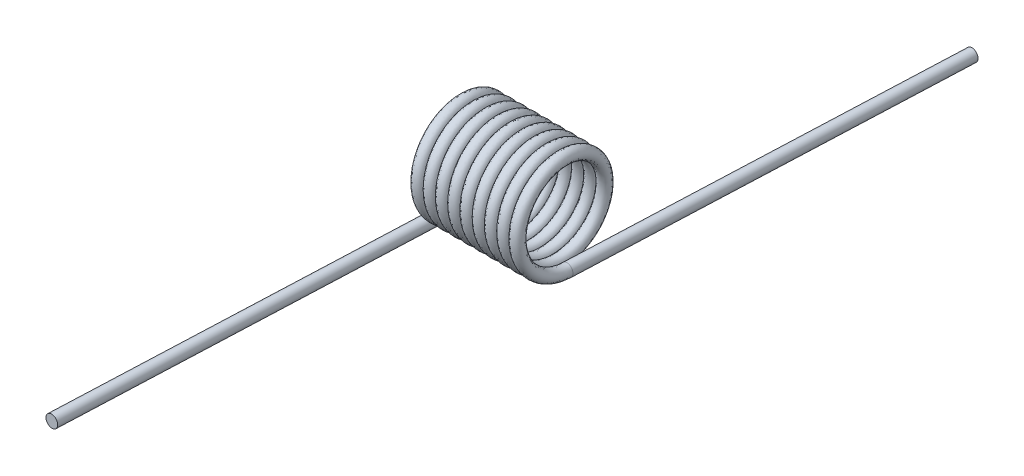
SolidWorks part; units mm, degrees
ref_plane "Front" through (0, 0, 0) normal (0, 0, 1) x (1, 0, 0)
ref_plane "Top" through (0, 0, 0) normal (0, 1, 0) x (1, 0, 0)
ref_plane "Right" through (0, 0, 0) normal (1, 0, 0) x (0, 0, -1)
sketch "Sketch1" plane through (0, 0, 0) normal (1, 0, 0) x (0, 0, -1)
  line L0 (0, -10.5664) -> (0, -13.7414) construction
  line L1 (0, -13.7414) -> (101.6, -13.7414) construction
  line L2 (0, -13.7414) -> (-101.6, -13.7414) construction
  line L3 (0, 0) -> (13.7414, 0) construction
  line L4 (0, 0) -> (0, -13.7414) construction
  line L5 (-101.6, -13.7414) -> (-101.6, -10.5664) construction
  line L6 (-101.6, -10.5664) -> (0, -10.5664) construction
  line L7 (101.6, -13.7414) -> (101.6, -10.5664) construction
  line L8 (101.6, -10.5664) -> (0, -10.5664) construction
  circle A0 centre (0, 0) radius 13.7414 construction
  circle A1 centre (0, 0) radius 8.4582 construction
  circle A2 centre (0, 0) radius 12.1539 construction
  point P7 (0, -12.1539)
  point P10 (0, 13.7414)
  dimension "OD" = 27.4828
  dimension "For Shaft Diameter" = 16.9164
  dimension "Wire Diameter" = 3.175
  dimension "Leg Length" = 101.6
  dimension "Deflection Angle" = 180
sketch "Sketch2" plane through (0, 0, 0) normal (1, 0, 0) x (0, 0, -1)
  circle A0 centre (0, 0) radius 12.1539 construction
  circle A2 centre (0, 0) radius 12.1539
curve "Helix/Spiral1" pitch 3.2004 height 28.8036 radius 12.1539 centre (0, 0, 0) axis (1, 0, 0) start towards (0, 0, -1)
ref_plane "Plane1" through (0, -12.1539, 0) normal (0.0419, 0, -0.9991) x (0.9989, -0.0232, 0.0419)
sketch "Sketch3" plane through (0, -12.1539, 0) normal (0.0419, 0, -0.9991) x (0.9989, -0.0232, 0.0419)
  circle A0 centre (0, 0) radius 1.5875
  dimension "D1" = 3.175
sweep "Sweep1" add profiles "Sketch3" path "Helix/Spiral1"
sketch "Sketch4" plane through (0, 0, 0) normal (-0.0419, 0, 0.9991) x (-0.9989, 0.0232, -0.0419)
  circle A1 centre (-0.2824, 12.1506) radius 1.5875
  circle A2 centre (-0.2824, 12.1506) radius 1.5875
  dimension "D1" = 0
extrude "Extrude1" add sketch "Sketch4" along normal blind 101.6
sketch "Sketch5" plane through (0.0505, 0, -1.205) normal (0.0419, 0, -0.9991) x (-0.9982, -0.0419, -0.0418)
  circle A1 centre (-28.244, -13.3486) radius 1.5875
  circle A2 centre (-28.244, -13.3486) radius 1.5875
  dimension "D1" = 0
extrude "Extrude2" add sketch "Sketch5" along normal blind 101.6
sketch "Sketch6" plane through (0, 0, 0) normal (1, 0, 0) x (0, 0, -1)
  circle A2 centre (0, 0) radius 10.5664 construction
equation "\"D4@Helix/Spiral1\" = \"Wire Diameter@Sketch1\" + .001"
equation "\"D1@Sketch3\"=\"Wire Diameter@Sketch1\""
equation "\"D1@Extrude2\"=\"Leg Length@Sketch1\""
equation "\"Leg Length@Extrude1\"=\"Leg Length@Sketch1\""
